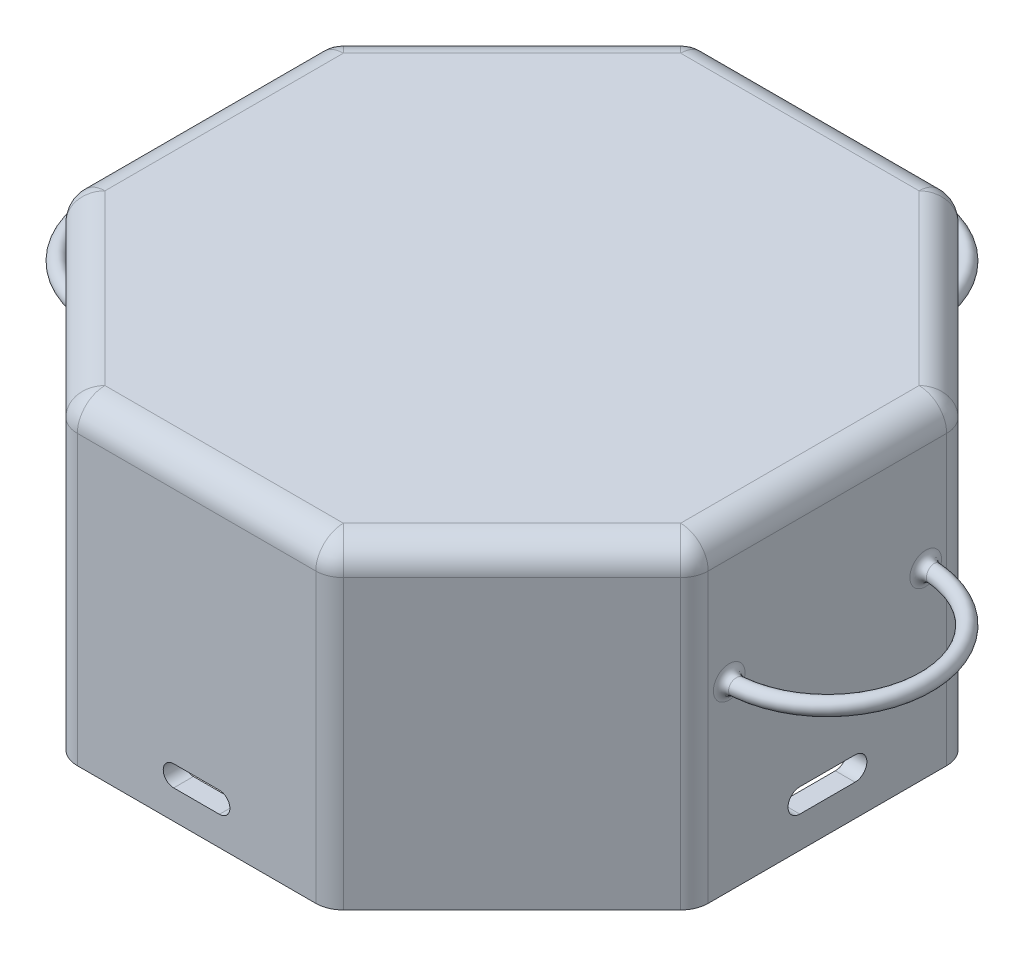
SolidWorks part; units mm, degrees
ref_plane "Front Plane" through (0, 0, 0) normal (0, 0, 1) x (1, 0, 0)
ref_plane "Top Plane" through (0, 0, 0) normal (0, 1, 0) x (1, 0, 0)
ref_plane "Right Plane" through (0, 0, 0) normal (1, 0, 0) x (0, 0, -1)
sketch "Sketch1" plane through (0, 0, 0) normal (0, 1, 0) x (1, 0, 0)
  line L1 (16.5685, 40) -> (-16.5685, 40)
  line L2 (-16.5685, 40) -> (-40, 16.5685)
  line L3 (-40, 16.5685) -> (-40, -16.5685)
  line L4 (-40, -16.5685) -> (-16.5685, -40)
  line L5 (-16.5685, -40) -> (16.5685, -40)
  line L6 (16.5685, -40) -> (40, -16.5685)
  line L7 (40, -16.5685) -> (40, 16.5685)
  line L8 (40, 16.5685) -> (16.5685, 40)
  circle A0 centre (0, 0) radius 40 construction
  point P1 (0, 40)
  dimension "D1" = 80
extrude "Boss-Extrude1" add sketch "Sketch1" along normal blind 40
sketch "Sketch2" plane through (0, 0, 0) normal (0, -1, 0) x (1, 0, 0)
  line L1 (37.5, 15.533) -> (15.533, 37.5)
  line L2 (15.533, 37.5) -> (-15.533, 37.5)
  line L3 (-15.533, 37.5) -> (-37.5, 15.533)
  line L4 (-37.5, 15.533) -> (-37.5, -15.533)
  line L5 (-37.5, -15.533) -> (-15.533, -37.5)
  line L6 (-15.533, -37.5) -> (15.533, -37.5)
  line L7 (15.533, -37.5) -> (37.5, -15.533)
  line L8 (37.5, -15.533) -> (37.5, 15.533)
  circle A0 centre (0, 0) radius 37.5 construction
  point P1 (0, 37.5)
  dimension "D1" = 75
extrude "Cut-Extrude1" cut sketch "Sketch2" against normal blind 37.5
fillet "Fillet1" radius 3.5 16 edges at (-40, 20, -16.5685) (-16.5685, 20, -40) (16.5685, 20, -40) (40, 20, -16.5685) (40, 40, 0) (28.2843, 40, -28.2843) (0, 40, -40) (-28.2843, 40, -28.2843) (-40, 40, 0) (-28.2843, 40, 28.2843) (0, 40, 40) (28.2843, 40, 28.2843) (40, 20, 16.5685) (16.5685, 20, 40) (-40, 20, 16.5685) (-16.5685, 20, 40)
sketch "Sketch3" plane through (0, 0, 40) normal (0, 0, 1) x (1, 0, 0)
  line L0 (-2.9, 5) -> (2.9, 5) construction
  line L1 (-2.9, 6.325) -> (2.9, 6.325)
  line L2 (-2.9, 3.675) -> (2.9, 3.675)
  arc A0 (-2.9, 6.325) -> (-2.9, 3.675) centre (-2.9, 5) ccw
  arc A1 (2.9, 3.675) -> (2.9, 6.325) centre (2.9, 5) ccw
  point P2 (0, 5)
  point P7 (-4.225, 5)
  point P8 (4.225, 5)
  point P9 (0, 0)
  dimension "D1" = 8.45
  dimension "D2" = 2.65
  dimension "D3" = 5
extrude "Cut-Extrude2" cut sketch "Sketch3" against normal up to surface (2.5 mm away) up to face at (0, 18.75, 37.5)
sketch "Sketch4" plane through (40, 0, 0) normal (1, 0, 0) x (0, 0, -1)
  line L0 (-3.5, 5.5) -> (3.5, 5.5) construction
  line L1 (-3.5, 7) -> (3.5, 7)
  line L2 (-3.5, 4) -> (3.5, 4)
  line L3 (44, 0) -> (-44, 0) construction
  arc A0 (-3.5, 7) -> (-3.5, 4) centre (-3.5, 5.5) ccw
  arc A1 (3.5, 4) -> (3.5, 7) centre (3.5, 5.5) ccw
  point P2 (0, 5.5)
  point P7 (-5, 5.5)
  point P8 (5, 5.5)
  point P9 (0, 0)
  dimension "D1" = 10
  dimension "D2" = 3
  dimension "D3" = 5.5
extrude "Cut-Extrude3" cut sketch "Sketch4" against normal up to surface (2.5 mm away) up to face at (37.5, 18.75, 0)
sketch "Sketch5" plane through (40, 0, 0) normal (1, 0, 0) x (0, 0, -1)
  line L0 (-12.5, 23) -> (12.5, 23) construction
  circle A0 centre (-12.5, 23) radius 1
  circle A1 centre (12.5, 23) radius 1
  point P5 (0, 0)
  point P6 (0, 23)
  dimension "D1" = 2
  dimension "D2" = 2
  dimension "D3" = 25
  dimension "D4" = 23
ref_plane "Plane1" through (0, 23, 0) normal (0, 1, 0) x (1, 0, 0)
sketch "Sketch7" plane through (0, 23, 0) normal (0, 1, 0) x (1, 0, 0)
  line L0 (40, -12.5) -> (40, 12.5) construction
  line L1 (40, -13.5) -> (40, -11.5) construction
  line L2 (40, 11.5) -> (40, 13.5) construction
  arc A0 (40, -12.5) -> (40, 12.5) centre (40, 0) ccw
sweep "Sweep1" add profiles "Sketch5" path "Sketch7"
fillet "Fillet2" radius 1 2 edges at (40, 23, 11.5) (40, 23, -11.5)
mirror "Mirror2" about plane through (0, 0, 0) normal (1, 0, 0) of "Cut-Extrude3", "Sweep1"
fillet "Fillet3" radius 1 2 edges at (-40, 23, 11.5) (-40, 23, -11.5)
sketch "Sketch9" plane through (0, 0, -40) normal (0, 0, -1) x (-1, 0, 0)
  line L0 (-12.5, 23) -> (12.5, 23) construction
  line L1 (44, 23) -> (-44, 23) construction
  circle A0 centre (-12.5, 23) radius 1
  circle A1 centre (12.5, 23) radius 1
  point P4 (0, 23)
  dimension "D1" = 2
  dimension "D2" = 2
  dimension "D3" = 25
sketch "Sketch10" plane through (0, 23, 0) normal (0, 1, 0) x (1, 0, 0)
  line L0 (12.5, 40) -> (-12.5, 40) construction
  line L1 (13.5, 40) -> (11.5, 40) construction
  line L2 (-11.5, 40) -> (-13.5, 40) construction
  arc A0 (-12.5, 40) -> (12.5, 40) centre (0, 40) cw
sweep "Sweep2" add profiles "Sketch9" path "Sketch10"
fillet "Fillet4" radius 1 2 edges at (13.5, 23, -40) (-11.5, 23, -40)
